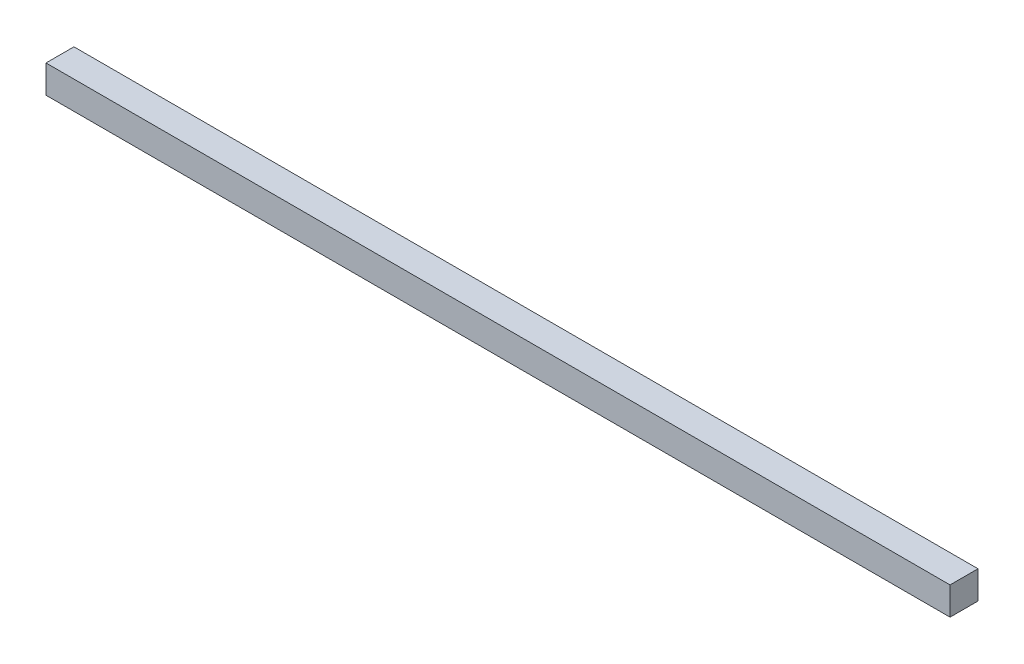
SolidWorks part; units mm, degrees
material "Plywood"
ref_plane "Front Plane" through (0, 0, 0) normal (0, 0, 1) x (1, 0, 0)
ref_plane "Top Plane" through (0, 0, 0) normal (0, 1, 0) x (1, 0, 0)
ref_plane "Right Plane" through (0, 0, 0) normal (1, 0, 0) x (0, 0, -1)
sketch "Sketch1" plane through (0, 0, 0) normal (1, 0, 0) x (0, 0, -1)
  line L1 (0, 0) -> (9.525, 0)
  line L2 (0, 0) -> (0, 9.525)
  line L3 (0, 9.525) -> (9.525, 9.525)
  line L4 (9.525, 0) -> (9.525, 9.525)
  dimension "D1" = 9.525
extrude "Boss-Extrude1" add sketch "Sketch1" against normal blind 307.975 contours L1 L4 L3 L2 region at (0, 4.7625, -4.7625)
move or copy body "Body-Move/Copy1" [suppressed] bodies to move or copy 101 parameters "D1"=0, "D2"=0, "D3"=0
move or copy body "Body-Move/Copy2" [suppressed] bodies to move or copy 102 parameters "D1"=0, "D2"=0, "D3"=0
move or copy body "Body-Move/Copy3" [suppressed] bodies to move or copy 103 parameters "D1"=0, "D2"=0, "D3"=0
move or copy body "Body-Move/Copy4" [suppressed] bodies to move or copy 104 parameters "D1"=0, "D2"=0, "D3"=0
